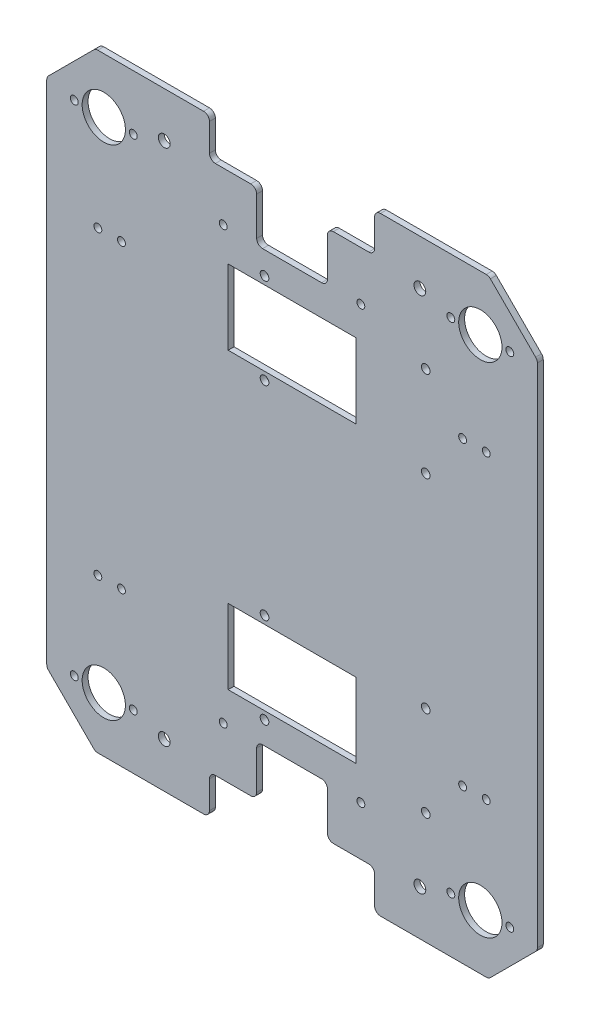
SolidWorks part; units mm, degrees
material "Alliage 1060"
ref_plane "Plan de dessus" through (0, 0, 0) normal (0, 0, 1) x (1, 0, 0)
ref_plane "Plan de droite" through (0, 0, 0) normal (0, 1, 0) x (1, 0, 0)
ref_plane "Plan de face" through (0, 0, 0) normal (1, 0, 0) x (0, 0, -1)
sketch "Esquisse1" plane through (0, 0, 0) normal (0, 0, 1) x (1, 0, 0)
  line L0 (0, 0) -> (-200, 0)
  line L1 (-200, 0) -> (-224.7487, 24.7487)
  line L2 (-224.7487, 24.7487) -> (-224.7487, 284.7487)
  line L3 (-224.7487, 284.7487) -> (-200, 309.4975)
  line L4 (-200, 309.4975) -> (0, 309.4975)
  line L5 (0, 309.4975) -> (24.7487, 284.7487)
  line L6 (24.7487, 284.7487) -> (24.7487, 24.7487)
  line L7 (24.7487, 24.7487) -> (0, 0)
  dimension "D1" = 260
  dimension "D2" = 35
  dimension "D3" = 135
  dimension "D4" = 200
extrude "Base" add sketch "Esquisse1" along normal blind 3
sketch "Esquisse3" plane through (0, 0, 0) normal (0, 0, -1) x (-1, 0, 0)
  line L0 (142, 0) -> (142, 20)
  line L1 (200, 0) -> (0, 0) construction
  line L2 (142, 20) -> (118, 20)
  line L3 (118, 20) -> (118, 45.5)
  line L4 (118, 45.5) -> (82, 45.5)
  line L5 (82, 45.5) -> (82, 20)
  line L6 (82, 20) -> (58, 20)
  line L7 (58, 20) -> (58, 0)
  line L8 (-24.7487, 154.7487) -> (224.7487, 154.7487) construction
  line L9 (-24.7487, 24.7487) -> (-24.7487, 284.7487) construction
  line L10 (224.7487, 284.7487) -> (224.7487, 24.7487) construction
  line L11 (58, 0) -> (142, 0)
  line L12 (58, 309.4975) -> (142, 309.4975)
  line L13 (142, 309.4975) -> (142, 289.4975)
  line L14 (142, 289.4975) -> (118, 289.4975)
  line L15 (118, 289.4975) -> (118, 263.9975)
  line L16 (118, 263.9975) -> (82, 263.9975)
  line L17 (82, 263.9975) -> (82, 289.4975)
  line L18 (82, 289.4975) -> (58, 289.4975)
  line L19 (58, 289.4975) -> (58, 309.4975)
  line L20 (100, 45.5) -> (100, -49954.5) construction
  line L21 (0, 309.4975) -> (200, 309.4975) construction
  line L22 (67.5, 244.4975) -> (132.5, 244.4975)
  line L23 (67.5, 244.4975) -> (67.5, 214.4975)
  line L24 (67.5, 214.4975) -> (132.5, 214.4975)
  line L25 (132.5, 244.4975) -> (132.5, 214.4975)
  line L26 (132.5, 65) -> (132.5, 95)
  line L27 (67.5, 95) -> (132.5, 95)
  line L28 (67.5, 65) -> (132.5, 65)
  line L29 (67.5, 65) -> (67.5, 95)
  circle A0 centre (65, 45) radius 2
  circle A1 centre (135, 45) radius 2
  circle A2 centre (135, 264.4975) radius 2
  circle A3 centre (65, 264.4975) radius 2
  point P4 (100, 45.5)
  point P11 (100, 0)
  point P40 (100, 244.4975)
  point P41 (132.5, 229.4975)
  dimension "D7" = 4
  dimension "D5" = 25
  dimension "D1" = 20
  dimension "D2" = 24
  dimension "D3" = 36
  dimension "D4" = 25.5
  dimension "D6" = 7
  dimension "D8" = 80
  dimension "D9" = 30
  dimension "D10" = 65
extrude "Perçage roues encodeuses" cut sketch "Esquisse3" against normal through all
fillet "Congé1" radius 3 24 edges at (-224.7487, 24.7487, 1.5) (24.7487, 24.7487, 1.5) (0, 0, 1.5) (-142, 20, 1.5) (-118, 45.5, 1.5) (-118, 20, 1.5) (-200, 0, 1.5) (-142, 0, 1.5) (-82, 45.5, 1.5) (-58, 20, 1.5) (-82, 20, 1.5) (-58, 0, 1.5) (24.7487, 284.7487, 1.5) (-142, 289.4975, 1.5) (-118, 263.9975, 1.5) (-224.7487, 284.7487, 1.5) (-200, 309.4975, 1.5) (-142, 309.4975, 1.5) (-118, 289.4975, 1.5) (-82, 263.9975, 1.5) (-58, 289.4975, 1.5) (-82, 289.4975, 1.5) (-58, 309.4975, 1.5) (0, 309.4975, 1.5)
sketch "Esquisse6" plane through (0, 0, 3) normal (0, 0, 1) x (1, 0, 0)
  line L0 (-195.7487, 28) -> (-210.7487, 28) construction
  line L1 (-195.7487, 28) -> (-180.7487, 28) construction
  line L2 (-100, 231.5685) -> (-100, -49768.4315) construction
  line L4 (-67.5, 214.4975) -> (-132.5, 214.4975) construction
  line L5 (-203.2843, 154.7487) -> (49796.7157, 154.7487) construction
  line L6 (-224.7487, 283.5061) -> (-224.7487, 25.9914) construction
  line L15 (-198.7574, 0) -> (-145, 0) construction
  circle A25 centre (-180.7487, 28) radius 2
  circle A26 centre (-210.7487, 28) radius 2
  circle A27 centre (-195.7487, 28) radius 11
  circle A31 centre (-19.2513, 28) radius 2
  circle A32 centre (10.7487, 28) radius 2
  circle A33 centre (-4.2513, 28) radius 11
  circle A34 centre (-4.2513, 281.4975) radius 11
  circle A35 centre (10.7487, 281.4975) radius 2
  circle A36 centre (-19.2513, 281.4975) radius 2
  circle A37 centre (-195.7487, 281.4975) radius 11
  circle A38 centre (-210.7487, 281.4975) radius 2
  circle A39 centre (-180.7487, 281.4975) radius 2
  point P15 (-100, 214.4975)
  point P20 (-224.7487, 154.7487)
  dimension "D2" = 4
  dimension "D3" = 15
  dimension "D4" = 15
  dimension "D5" = 180
  dimension "D9" = 29
  dimension "D13" = 22
  dimension "D15" = 28
extrude "Perçage billes porteuses" cut sketch "Esquisse6" against normal up to next
sketch "Esquisse8" plane through (0, 0, 3) normal (0, 0, 1) x (1, 0, 0)
  line L0 (-100, 263.9975) -> (-100, 95) construction
  line L1 (-85, 263.9975) -> (-115, 263.9975) construction
  line L2 (-132.5, 95) -> (-67.5, 95) construction
  line L3 (-145, 309.4975) -> (-198.7574, 309.4975) construction
  line L4 (-142, 292.4975) -> (-142, 306.4975) construction
  line L5 (-198.7574, 0) -> (-145, 0) construction
  line L6 (-142, 3) -> (-142, 17) construction
  circle A0 centre (-165, 23) radius 3
  circle A1 centre (-165, 286.4975) radius 3
  circle A2 centre (-35, 286.4975) radius 3
  circle A3 centre (-35, 23) radius 3
  dimension "D1" = 23
  dimension "D2" = 23
  dimension "D3" = 6
  dimension "D4" = 23
  dimension "D5" = 23
  dimension "D6" = 6
extrude "Perçage profilés" cut sketch "Esquisse8" against normal up to next
sketch "Esquisse10" plane through (0, 0, 3) normal (0, 0, 1) x (1, 0, 0)
  line L0 (-224.7487, 283.5061) -> (-224.7487, 25.9914) construction
  line L1 (-100, 214.4975) -> (-100, 95) construction
  line L2 (-123.75, 179.6975) -> (-100, 179.6975) construction
  line L3 (-67.5, 214.4975) -> (-132.5, 214.4975) construction
  line L4 (-100, 179.6975) -> (21.8665, 179.6975) construction
  line L5 (-224.7487, 154.7487) -> (24.7487, 154.7487) construction
  line L6 (24.7487, 25.9914) -> (24.7487, 283.5061) construction
  line L7 (-132.5, 95) -> (-67.5, 95) construction
  line L8 (-158.75, 179.6975) -> (-123.75, 179.6975) construction
  line L9 (-132.5, 229.4975) -> (-67.5, 229.4975) construction
  line L10 (-132.5, 214.4975) -> (-132.5, 244.4975) construction
  line L11 (-67.5, 244.4975) -> (-67.5, 214.4975) construction
  line L12 (-100, 129.8) -> (-139.6239, 129.8) construction
  line L13 (-100, 129.8) -> (10.2968, 129.8) construction
  circle A8 centre (-123.75, 179.6975) radius 1.75
  circle A9 centre (-120, 208.4975) radius 1.75
  circle A10 centre (-158.75, 179.6975) radius 1.75
  circle A11 centre (-80, 208.4975) radius 1.75
  circle A18 centre (-80, 101) radius 1.75
  circle A19 centre (-120, 101) radius 1.75
  circle A20 centre (-71.75, 179.6975) radius 1.75
  circle A21 centre (-40.75, 179.6975) radius 1.75
  circle A22 centre (-128.25, 129.8) radius 1.75
  circle A23 centre (-159.25, 129.8) radius 1.75
  circle A24 centre (-76.25, 129.8) radius 1.75
  circle A25 centre (-41.25, 129.8) radius 1.75
  dimension "D1" = 3.5
  dimension "D2" = 23.75
  dimension "D3" = 20
  dimension "D4" = 3.5
  dimension "D5" = 3.5
  dimension "D6" = 35
  dimension "D7" = 21
  dimension "D8" = 28.8
  dimension "D9" = 3.5
  dimension "D10" = 3.5
  dimension "D12" = 31
  dimension "D13" = 28.8
  dimension "D14" = 3.5
  dimension "D15" = 3.5
  dimension "D16" = 3.5
  dimension "D17" = 3.5
  dimension "D18" = 28.25
  dimension "D19" = 31
  dimension "D21" = 35
  dimension "D11" = 28.25
  dimension "D20" = 23.75
sketch "Esquisse15" plane through (0, 0, 0) normal (0, 0, -1) x (-1, 0, 0)
  line L0 (114, 103) -> (32, 103) construction
  line L1 (-24.7487, 154.7487) -> (23.202, 154.7487) construction
  line L2 (-24.7487, 25.9914) -> (-24.7487, 283.5061) construction
  line L3 (100, 95) -> (100, 134.4542) construction
  line L4 (132.5, 95) -> (67.5, 95) construction
  line L5 (0, 80) -> (59.1109, 80) construction
  line L6 (55, 0) -> (1.2426, 0) construction
  circle A0 centre (114, 103) radius 2.2
  circle A1 centre (32, 103) radius 2.2
  circle A2 centre (114, 57) radius 2.2
  circle A3 centre (32, 57) radius 2.2
  circle A4 centre (32, 252.4975) radius 2.2
  circle A5 centre (114, 252.4975) radius 2.2
  circle A6 centre (114, 206.4975) radius 2.2
  circle A7 centre (32, 206.4975) radius 2.2
  dimension "D2" = 4.4
  dimension "D1" = 82
  dimension "D3" = 80
  dimension "D4" = 23
  dimension "D5" = 14
extrude "Perçage bloc moteur" cut sketch "Esquisse15" against normal up to surface (3 mm away) up to face at (-38, 23, 3)
sketch "Esquisse16" plane through (0, 0, 0) normal (0, 0, -1) x (-1, 0, 0)
  line L0 (224.7487, 154.7487) -> (-24.7487, 154.7487) construction
  line L1 (67.5, 61) -> (132.5, 61)
  line L2 (67.5, 61) -> (67.5, 99)
  line L3 (67.5, 99) -> (132.5, 99)
  line L4 (132.5, 61) -> (132.5, 99)
  line L5 (224.7487, 283.5061) -> (224.7487, 25.9914) construction
  line L6 (-24.7487, 25.9914) -> (-24.7487, 283.5061) construction
  line L7 (100, 309.4975) -> (100, 0) construction
  line L8 (100, 0) -> (55, 0) construction
  line L9 (67.5, 210.4975) -> (132.5, 210.4975)
  line L10 (132.5, 248.4975) -> (132.5, 210.4975)
  line L11 (67.5, 248.4975) -> (132.5, 248.4975)
  line L12 (67.5, 248.4975) -> (67.5, 210.4975)
  line L13 (198.7574, 0) -> (145, 0) construction
  point P10 (132.5, 80)
  point P13 (100, 154.7487)
  point P16 (100, 61)
  dimension "D1" = 80
  dimension "D2" = 38
  dimension "D3" = 65
extrude "Enlèv. mat.-Extru.1" cut sketch "Esquisse16" against normal through all
sketch "Esquisse14" plane through (0, 309.4975, 0) normal (0, 1, 0) x (1, 0, 0)
  line L0 (-100, -3) -> (-100, 0) construction
  line L1 (-85, -3) -> (-115, -3) construction
  line L2 (-85, 0) -> (-115, 0) construction
sketch "Esquisse17" plane through (0, 0, 0) normal (0, 0, -1) x (-1, 0, 0)
  line L0 (-24.7487, 154.7487) -> (224.7487, 154.7487) construction
  line L1 (-24.7487, 25.9914) -> (-24.7487, 283.5061) construction
  line L2 (224.7487, 283.5061) -> (224.7487, 25.9914) construction
  line L3 (192.7487, 78.2487) -> (192.7487, 231.2487) construction
  line L4 (186.7487, 231.2487) -> (198.7487, 231.2487) construction
  line L5 (100, 309.4975) -> (100, 0) construction
  circle A0 centre (198.7487, 231.2487) radius 2
  circle A1 centre (186.7487, 231.2487) radius 2
  circle A2 centre (198.7487, 78.2487) radius 2
  circle A3 centre (186.7487, 78.2487) radius 2
  circle A4 centre (1.2513, 78.2487) radius 2
  circle A5 centre (13.2513, 78.2487) radius 2
  circle A6 centre (13.2513, 231.2487) radius 2
  circle A7 centre (1.2513, 231.2487) radius 2
  point P9 (192.7487, 154.7487)
  point P12 (192.7487, 231.2487)
  point P21 (100, 154.7487)
  dimension "D3" = 4
  dimension "D1" = 153
  dimension "D2" = 12
  dimension "D4" = 32
extrude "Perçage actionneur Main_De_Dieu" cut sketch "Esquisse17" against normal up to next
